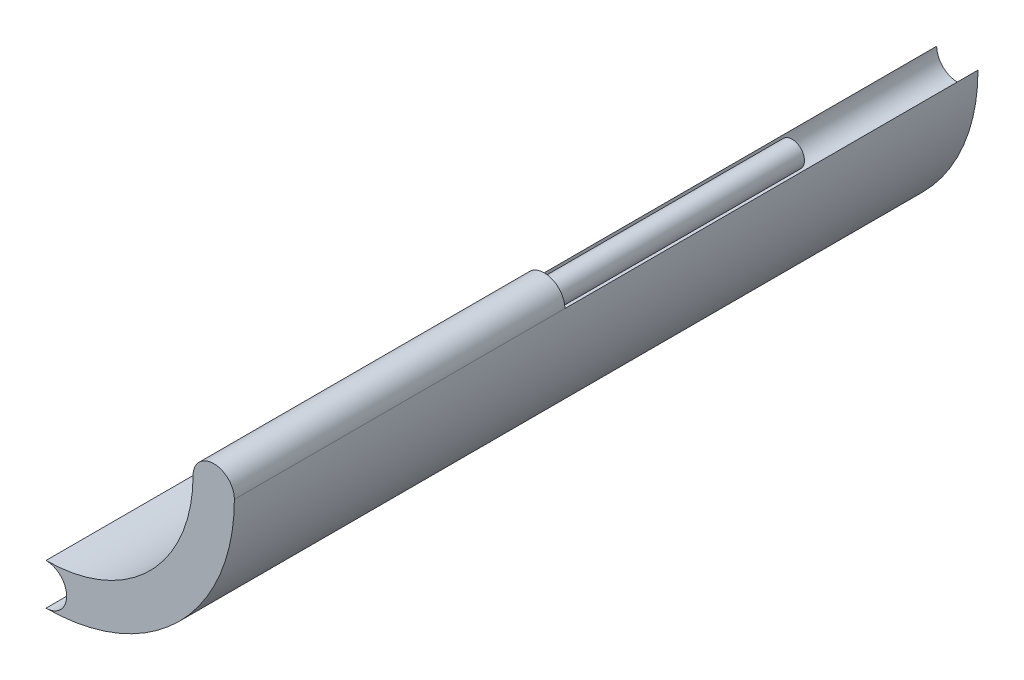
SolidWorks part; units mm, degrees
material "Commercialement pur CP-Ti UNS R50400 (SS)"
ref_plane "Plan de face" through (0, 0, 0) normal (0, 0, 1) x (1, 0, 0)
ref_plane "Plan de dessus" through (0, 0, 0) normal (0, 1, 0) x (1, 0, 0)
ref_plane "Plan de droite" through (0, 0, 0) normal (1, 0, 0) x (0, 0, -1)
sketch "Esquisse1" plane through (0, 0, 0) normal (0, 0, 1) x (1, 0, 0)
  line L0 (-114, 0) -> (114, 0) construction
  line L1 (0, -89) -> (0, -114) construction
  line L2 (89, 0) -> (114, 0) construction
  circle A0 centre (0, 0) radius 89
  circle A1 centre (0, 0) radius 114
  circle A2 centre (0, -101.5) radius 12.5
  circle A3 centre (101.5, 0) radius 12.5
  circle A4 centre (101.5, 0) radius 7.5
  dimension "D1" = 228
  dimension "D2" = 178
  dimension "D3" = 15
extrude "Boss.-Extru.1" add sketch "Esquisse1" against normal blind 450 contours A3 A0 A2 A1 region at (66.5645, -66.5645, 0)
extrude "Boss.-Extru.2" add sketch "Esquisse1<3>" against normal blind 350 separate body contours A4 region at (101.5, 0, 0)
sketch "Esquisse1<3>" plane through (0, 0, 0) normal (0, 0, 1) x (1, 0, 0) same geometry as "Esquisse1"
extrude "Boss.-Extru.3" add sketch "Esquisse1<4>" against normal blind 200 contours A3 A4 region at (101.5, 12.1464, 0)
sketch "Esquisse1<4>" plane through (0, 0, 0) normal (0, 0, 1) x (1, 0, 0) same geometry as "Esquisse1"
